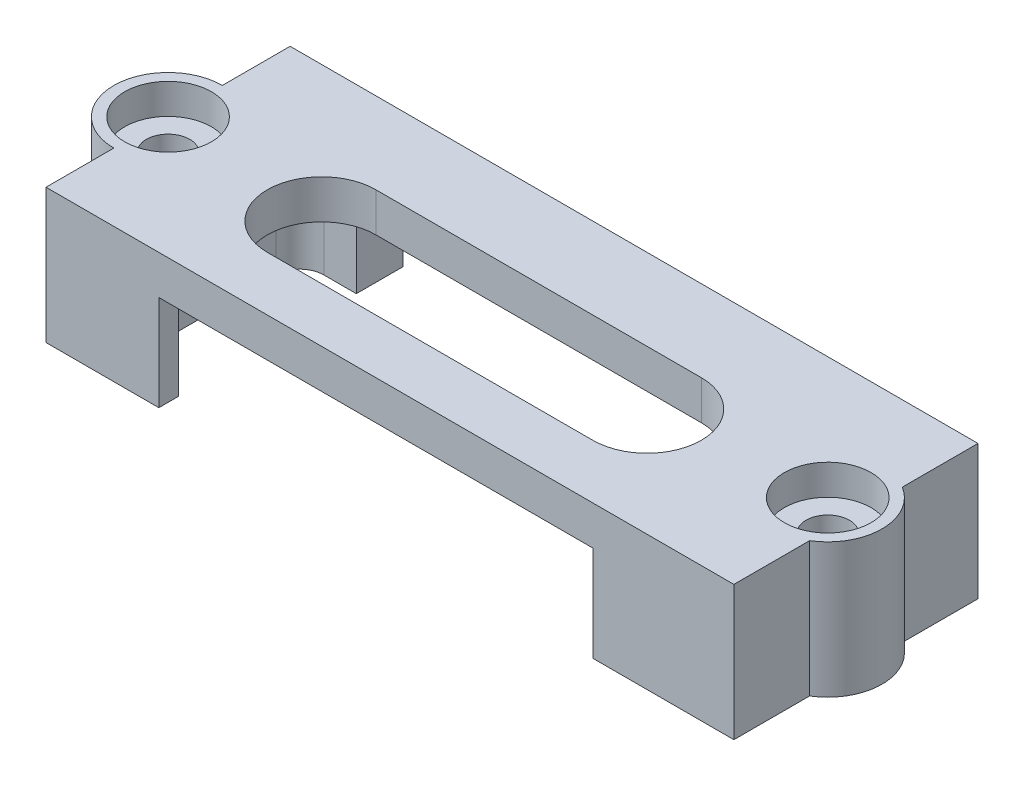
SolidWorks part; units mm, degrees
material "6061 合金"
ref_plane "前视基准面" through (0, 0, 0) normal (0, 0, 1) x (1, 0, 0)
ref_plane "上视基准面" through (0, 0, 0) normal (0, 1, 0) x (1, 0, 0)
ref_plane "右视基准面" through (0, 0, 0) normal (1, 0, 0) x (0, 0, -1)
other "Configuration Table"
sketch "草图1" plane through (0, 0, 0) normal (0, 1, 0) x (1, 0, 0)
  line L0 (0, 0) -> (0, -12.8362) construction
  line L1 (-15.85, -5.625) -> (15.85, -5.625)
  line L2 (-15.85, -5.625) -> (-15.85, -2.5)
  line L3 (-15.85, 5.625) -> (15.85, 5.625)
  line L4 (15.85, -5.625) -> (15.85, -2.1354)
  line L5 (-15.85, -5.625) -> (15.85, 5.625) construction
  line L6 (-15.85, 5.625) -> (15.85, -5.625) construction
  line L7 (-15.85, 2.5) -> (-15.85, 5.625)
  line L8 (15.85, 2.1354) -> (15.85, 5.625)
  line L9 (0, 0) -> (-15.85, 0) construction
  line L10 (0, 0) -> (14.55, 0) construction
  arc A0 (-15.85, 2.5) -> (-15.85, -2.5) centre (-15.85, 0) ccw
  arc A1 (15.85, 2.1354) -> (15.85, -2.1354) centre (14.55, 0) cw
  point P0 (0, 0)
  dimension "D3" = 5
  dimension "D1" = 31.7
  dimension "D2" = 11.25
  dimension "D4" = 30.4
extrude "凸台-拉伸1" add sketch "草图1" along normal blind 6.2
sketch "草图2" plane through (0, 0, 0) normal (0, -1, 0) x (1, 0, 0)
  line L0 (-15.85, 5.625) -> (15.85, 5.625) construction
  line L1 (-10.65, -5.625) -> (9.35, -5.625)
  line L2 (-10.65, -5.625) -> (-10.65, 5.625)
  line L3 (-10.65, 5.625) -> (9.35, 5.625)
  line L4 (9.35, -5.625) -> (9.35, 5.625)
  line L5 (-10.65, -5.625) -> (9.35, 5.625) construction
  line L6 (-10.65, 5.625) -> (9.35, -5.625) construction
  line L7 (-0.65, 0) -> (0, 0) construction
  line L8 (-15.85, 2.5) -> (-15.85, 5.625) construction
  point P0 (-0.65, 0)
  dimension "D1" = 20
  dimension "D2" = 5.2
extrude "切除-拉伸1" cut sketch "草图2" against normal blind 4.4
sketch "草图3" plane through (0, 0, 0) normal (0, -1, 0) x (1, 0, 0)
  line L1 (-12.15, 4.625) -> (10.85, 4.625)
  line L2 (-13.15, 3.625) -> (-13.15, -2.375)
  line L3 (-12.15, -3.375) -> (10.85, -3.375)
  line L4 (11.85, 3.625) -> (11.85, -2.375)
  line L5 (9.35, 5.625) -> (-10.65, 5.625) construction
  line L6 (-15.85, 2.5) -> (-15.85, 5.625) construction
  arc A0 (10.85, 4.625) -> (11.85, 3.625) centre (10.85, 3.625) cw
  arc A1 (10.85, -3.375) -> (11.85, -2.375) centre (10.85, -2.375) ccw
  arc A2 (-13.15, -2.375) -> (-12.15, -3.375) centre (-12.15, -2.375) ccw
  arc A3 (-12.15, 4.625) -> (-13.15, 3.625) centre (-12.15, 3.625) ccw
  point P8 (11.85, 4.625)
  point P11 (11.85, -3.375)
  point P14 (-13.15, -3.375)
  dimension "D4" = 1
  dimension "D1" = 2.7
  dimension "D2" = 8
  dimension "D3" = 25
  dimension "D5" = 1
extrude "切除-拉伸2" cut sketch "草图3" against normal blind 4.4
sketch "草图4" plane through (0, 6.2, 0) normal (0, 1, 0) x (1, 0, 0)
  circle A0 centre (-15.85, 0) radius 1
  circle A1 centre (14.55, 0) radius 1
  dimension "D1" = 2
extrude "切除-拉伸3" cut sketch "草图4" against normal through all
sketch "草图5" plane through (0, 6.2, 0) normal (0, 1, 0) x (1, 0, 0)
  line L0 (0, -8.5574) -> (0, 0) construction
  circle A0 centre (-15.85, 0) radius 2
  circle A1 centre (14.55, 0) radius 2
  circle A2 centre (14.55, 0) radius 1 construction
  dimension "D1" = 4
extrude "切除-拉伸4" cut sketch "草图5" against normal blind 1.4
sketch "草图6" plane through (0, 0, 0) normal (0, -1, 0) x (1, 0, 0)
  line L0 (-12.15, -3.375) -> (10.85, -3.375) construction
  line L1 (11.85, 3.625) -> (11.85, -2.375) construction
  line L2 (-12.15, 4.625) -> (10.85, 4.625) construction
  line L3 (-13.15, 3.625) -> (-13.15, -2.375) construction
  line L4 (11.85, 3.625) -> (11.85, -2.375) construction
  line L5 (-12.15, 4.625) -> (10.85, 4.625) construction
  line L6 (-13.15, 3.625) -> (-13.15, -2.375) construction
  line L7 (-12.15, -3.375) -> (10.85, -3.375) construction
  line L8 (11.95, 3.625) -> (11.95, -2.375)
  line L9 (-12.15, 4.725) -> (10.85, 4.725)
  line L10 (-13.25, 3.625) -> (-13.25, -2.375)
  line L11 (-12.15, -3.475) -> (10.85, -3.475)
  arc A0 (-13.15, -2.375) -> (-12.15, -3.375) centre (-12.15, -2.375) ccw construction
  arc A1 (10.85, -3.375) -> (11.85, -2.375) centre (10.85, -2.375) ccw construction
  arc A2 (11.85, 3.625) -> (10.85, 4.625) centre (10.85, 3.625) ccw construction
  arc A3 (-12.15, 4.625) -> (-13.15, 3.625) centre (-12.15, 3.625) ccw construction
  arc A4 (10.85, -3.375) -> (11.85, -2.375) centre (10.85, -2.375) ccw construction
  arc A5 (11.85, 3.625) -> (10.85, 4.625) centre (10.85, 3.625) ccw construction
  arc A6 (-12.15, 4.625) -> (-13.15, 3.625) centre (-12.15, 3.625) ccw construction
  arc A7 (-13.15, -2.375) -> (-12.15, -3.375) centre (-12.15, -2.375) ccw construction
  arc A8 (10.85, -3.475) -> (11.95, -2.375) centre (10.85, -2.375) ccw
  arc A9 (11.95, 3.625) -> (10.85, 4.725) centre (10.85, 3.625) ccw
  arc A10 (-12.15, 4.725) -> (-13.25, 3.625) centre (-12.15, 3.625) ccw
  arc A11 (-13.25, -2.375) -> (-12.15, -3.475) centre (-12.15, -2.375) ccw
  dimension "D1" = 0.1
extrude "切除-拉伸5" cut sketch "草图6" against normal blind 4.4
sketch "草图7" plane through (0, 4.4, 0) normal (0, -1, 0) x (1, 0, 0)
  line L0 (-13.25, 0.625) -> (-0.65, 0.625) construction
  line L1 (-13.25, 3.625) -> (-13.25, -2.375) construction
  line L2 (-0.65, 0.625) -> (11.95, 0.625) construction
  line L3 (-8.15, 0.625) -> (6.85, 0.625) construction
  line L4 (-8.15, 3.125) -> (6.85, 3.125)
  line L5 (-8.15, -1.875) -> (6.85, -1.875)
  line L6 (11.95, -2.375) -> (11.95, 3.625) construction
  arc A0 (-8.15, 3.125) -> (-8.15, -1.875) centre (-8.15, 0.625) ccw
  arc A1 (6.85, -1.875) -> (6.85, 3.125) centre (6.85, 0.625) ccw
  point P8 (-0.65, 0.625)
  dimension "D1" = 5
  dimension "D2" = 15
extrude "切除-拉伸6" cut sketch "草图7" against normal blind 4.2
sketch "草图8" plane through (0, 0, 0) normal (0, 1, 0) x (1, 0, 0)
  line L0 (15.85, 5.625) -> (-15.85, 5.625) construction
  line L1 (9.85, 5.625) -> (12.85, 5.625)
  line L2 (9.85, 5.625) -> (9.85, 9.625)
  line L3 (9.85, 9.625) -> (12.85, 9.625)
  line L4 (12.85, 5.625) -> (12.85, 9.625)
  line L5 (15.85, 2.1354) -> (15.85, 5.625) construction
  dimension "D1" = 3
  dimension "D2" = 4
  dimension "D3" = 3
extrude "凸台-拉伸2" [suppressed] add sketch "草图8" against normal blind 1 from surface
pattern_linear "阵列(线性)1" [suppressed] count 2 spacing 15 of bodies 114
pattern_linear "阵列(线性)2" [suppressed] count 2 spacing 30
sketch "草图9" [suppressed] plane through (0, 0, 0) normal (0, 1, 0) x (1, 0, 0)
  line L1 (9.85, 54.625) -> (12.85, 54.625)
  line L2 (9.85, 54.625) -> (9.85, 50.625)
  line L3 (9.85, 50.625) -> (12.85, 50.625)
  line L4 (12.85, 54.625) -> (12.85, 50.625)
extrude "切除-拉伸9" [suppressed] cut sketch "草图9" along normal through all
sketch "草图11" [suppressed] plane through (0, 5.2, 0) normal (0, -1, 0) x (1, 0, 0)
  line L4 (12.85, -24.625) -> (12.85, -20.625)
  line L5 (12.85, -20.625) -> (9.85, -20.625)
  line L6 (9.85, -20.625) -> (9.85, -24.625)
  line L7 (9.85, -24.625) -> (12.85, -24.625)
  line L8 (12.85, -24.625) -> (12.85, -20.625)
  line L9 (12.85, -20.625) -> (9.85, -20.625)
  line L10 (9.85, -20.625) -> (9.85, -24.625)
  line L11 (9.85, -24.625) -> (12.85, -24.625)
  dimension "D1" = 0
extrude "切除-拉伸11" [suppressed] cut sketch "草图11" against normal blind 6
